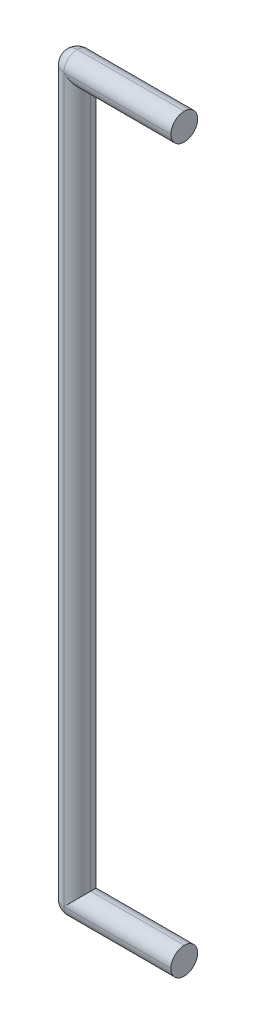
SolidWorks part; units mm, degrees
ref_plane "Front" through (0, 0, 0) normal (0, 0, 1) x (1, 0, 0)
ref_plane "Top" through (0, 0, 0) normal (0, 1, 0) x (1, 0, 0)
ref_plane "Right" through (0, 0, 0) normal (1, 0, 0) x (0, 0, -1)
sketch "草图1" plane through (0, 0, 0) normal (0, 1, 0) x (1, 0, 0)
  line L1 (0.5, -0.5) -> (-0.5, -0.5)
  line L2 (0.5, -0.5) -> (0.5, 0.5)
  line L3 (0.5, 0.5) -> (-0.5, 0.5)
  line L4 (-0.5, -0.5) -> (-0.5, 0.5)
  line L5 (0.5, -0.5) -> (-0.5, 0.5) construction
  line L6 (0.5, 0.5) -> (-0.5, -0.5) construction
  point P0 (0, 0)
  dimension "D1" = 1
  dimension "D2" = 1
extrude "凸台-拉伸1" add sketch "草图1" along normal blind 26
sketch "草图2" plane through (0, 0, 0) normal (1, 0, 0) x (0, 0, -1)
  line L0 (-0.5, 0) -> (0.5, 0) construction
  line L1 (-0.5, -1) -> (0.5, -1)
  line L2 (-0.5, -1) -> (-0.5, 0)
  line L3 (-0.5, 0) -> (0.5, 0)
  line L4 (0.5, -1) -> (0.5, 0)
  line L5 (-0.5, -1) -> (0.5, 0) construction
  line L6 (-0.5, 0) -> (0.5, -1) construction
  line L7 (0, 1.8428) -> (0, -2.8428) construction
  line L8 (-0.5, 26) -> (0.5, 26) construction
  line L9 (0.5, 26) -> (-0.5, 26)
  line L10 (0.5, 26) -> (0.5, 27)
  line L11 (0.5, 27) -> (-0.5, 27)
  line L12 (-0.5, 26) -> (-0.5, 27)
  line L13 (0.5, 26) -> (-0.5, 27) construction
  line L14 (0.5, 27) -> (-0.5, 26) construction
  point P0 (0, -0.5)
  point P10 (0.5, 26.5)
  point P11 (0, 26.5)
  dimension "D1" = 1
  dimension "D2" = 1
  dimension "D3" = 1
  dimension "D4" = 1
extrude "凸台-拉伸2" add sketch "草图2" along normal blind 4 and the other way blind 0.5
fillet "圆角1" radius 0.5 4 edges at (1.75, -1, 0.5) (2.25, 0, 0.5) (2.25, 0, -0.5) (1.75, -1, -0.5)
fillet "圆角2" radius 0.5 6 edges at (-0.5, -0.8536, -0.3536) (-0.5, -0.8536, 0.3536) (-0.5, 13.25, -0.5) (-0.5, 13.25, 0.5) (0.5, 12.75, -0.5) (0.5, 12.75, 0.5)
fillet "圆角3" radius 0.5 6 edges at (2, 27, 0.5) (-0.3536, 27, 0.3536) (-0.3536, 27, -0.3536) (2, 26, 0.5) (2, 26, -0.5) (2, 27, -0.5)
